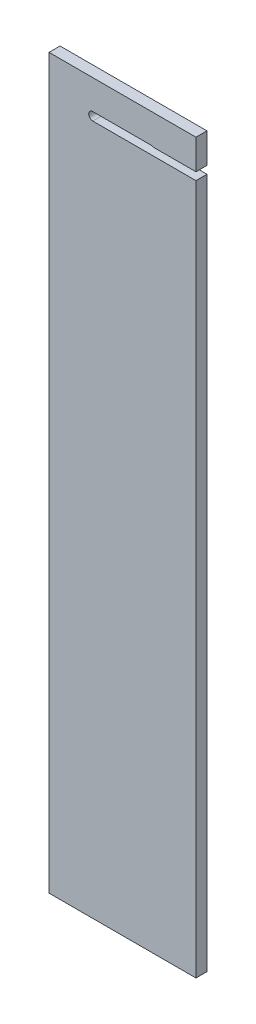
SolidWorks part; units mm, degrees
ref_plane "Front Plane" through (0, 0, 0) normal (0, 0, 1) x (1, 0, 0)
ref_plane "Top Plane" through (0, 0, 0) normal (0, 1, 0) x (1, 0, 0)
ref_plane "Right Plane" through (0, 0, 0) normal (1, 0, 0) x (0, 0, -1)
sketch "Sketch1" plane through (0, 0, 0) normal (0, 0, 1) x (1, 0, 0)
  line L0 (0, 149.225) -> (0, -149.225) construction
  line L1 (-31.75, 149.225) -> (31.75, 149.225)
  line L2 (-31.75, 149.225) -> (-31.75, -149.225)
  line L3 (-31.75, -149.225) -> (31.75, -149.225)
  line L4 (31.75, 149.225) -> (31.75, -149.225)
  line L5 (31.75, 152.527) -> (12.827, 152.527)
  line L10 (0, 149.225) -> (0, 165.481) construction
  line L11 (12.827, 152.527) -> (12.827, 152.781)
  line L12 (-31.75, 149.225) -> (31.75, 149.225)
  line L13 (-31.75, 149.225) -> (-31.75, 165.481)
  line L14 (-31.75, 165.481) -> (31.75, 165.481)
  line L15 (31.75, 149.225) -> (31.75, 165.481)
  line L16 (12.827, 152.781) -> (-12.827, 152.781)
  line L17 (-12.827, 152.781) -> (-12.827, 149.225)
  arc A0 (-12.827, 152.781) -> (-12.827, 149.225) centre (-12.827, 151.003) ccw
  point P6 (0, 0)
  point P21 (0, 152.781)
  dimension "D3" = 12.7
  dimension "D1" = 298.45
  dimension "D2" = 63.5
  dimension "D4" = 0.254
  dimension "D5" = 3.302
  dimension "D6" = 25.654
extrude "Boss-Extrude1" add sketch "Sketch1" along normal blind 4.7625 contours L4 L12 L1 L2 L3 | L17 L16 L11 L5 L15 L14 L13 L1 region at (-1.517, 158.5155, 0) region at (0, 0, 0)
fillet "Fillet1" radius 3.175 1 edges at (12.827, 152.527, 2.3813)
equation "\"Height\"= 12in"
equation "\"Depth\"= 7in"
equation "\"WallThickness\"= 0.1875in"
equation "\"FloorThickness\"= 0.1875in"
equation "\"Width\" = 30in"
equation "\"D1@Boss-Extrude1\"=\"WallThickness\""
